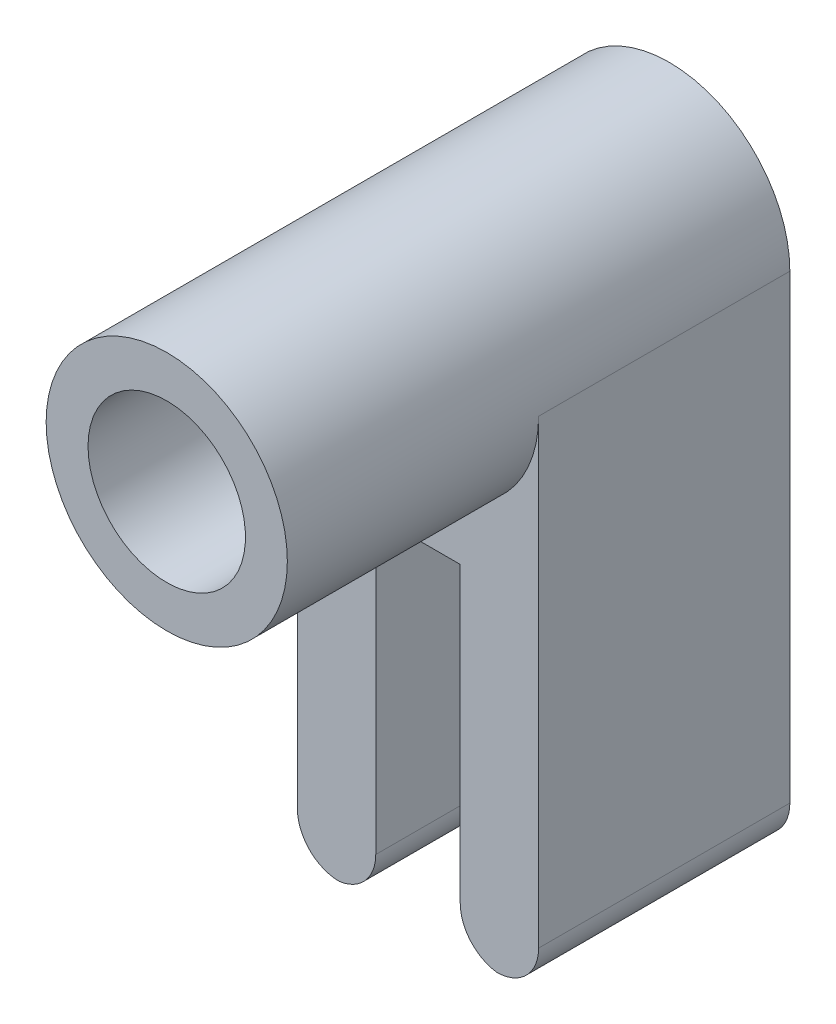
SolidWorks part; units mm, degrees
ref_plane "Front Plane" through (0, 0, 0) normal (0, 0, 1) x (1, 0, 0)
ref_plane "Top Plane" through (0, 0, 0) normal (0, 1, 0) x (1, 0, 0)
ref_plane "Right Plane" through (0, 0, 0) normal (1, 0, 0) x (0, 0, -1)
sketch "Sketch1" plane through (0, 0, 0) normal (0, 0, 1) x (1, 0, 0)
  circle A0 centre (0, 0) radius 2.3876
  circle A1 centre (0, 0) radius 3.6576
  dimension "D1" = 4.7752
  dimension "D2" = 1.27
extrude "Boss-Extrude1" add sketch "Sketch1" along normal blind 7.62
sketch "Sketch4" plane through (0, 0, 0) normal (0, 0, -1) x (-1, 0, 0)
  line L0 (-3.6576, 0) -> (-3.6576, -15.24)
  line L1 (-3.6576, -15.24) -> (3.6576, -15.24)
  line L2 (3.6576, -15.24) -> (3.6576, 0)
  circle A0 centre (0, 0) radius 3.6576 construction
  arc A1 (3.6576, 0) -> (-3.6576, 0) centre (0, 0) ccw
  dimension "D1" = 15.24
extrude "Boss-Extrude2" add sketch "Sketch4" along normal blind 7.62
fillet "Fillet1" radius 1.27 2 edges at (-3.6576, -15.24, -3.81) (3.6576, -15.24, -3.81)
sketch "Sketch5" plane through (0, -15.24, 0) normal (0, -1, 0) x (1, 0, 0)
  line L0 (2.3876, 0) -> (-2.3876, 0) construction
  line L1 (-1.2811, 0) -> (1.2811, 0)
  line L2 (-1.2811, 0) -> (-1.2811, -7.62)
  line L3 (-1.2811, -7.62) -> (1.2811, -7.62)
  line L4 (1.2811, 0) -> (1.2811, -7.62)
  line L5 (2.3876, -7.62) -> (-2.3876, -7.62) construction
  point P8 (0, 0)
  point P9 (0, 0)
  dimension "D1" = 2.5622
extrude "Cut-Extrude1" cut sketch "Sketch5" against normal blind 10.16
fillet "Fillet2" radius 1.27 2 edges at (1.2811, -15.24, -3.81) (-1.2811, -15.24, -3.81)
hole_wizard "M3 Clearance Hole1" positions "Sketch6" profile "Sketch7" hole size "M3" standard "ANSI Metric" end condition through all
sketch "Sketch6" plane through (0, 0, 0) normal (0, 0, 1) x (1, 0, 0)
  point P0 (0, 0)
sketch "Sketch7" plane through (0, 0, 0) normal (1, 0, 0) x (0, -1, 0)
  line L0 (0, 0) -> (0, 7.62)
  line L1 (0, 7.62) -> (1.8, 7.62)
  line L2 (1.8, 7.62) -> (1.8, 0)
  line L5 (1.8, 0) -> (0, 0)
  line L11 (0, -6.35) -> (0, 107.95) construction
  dimension "Thru Hole Dia." = 3.6
  dimension "Thru Hole Depth" = 7.62
